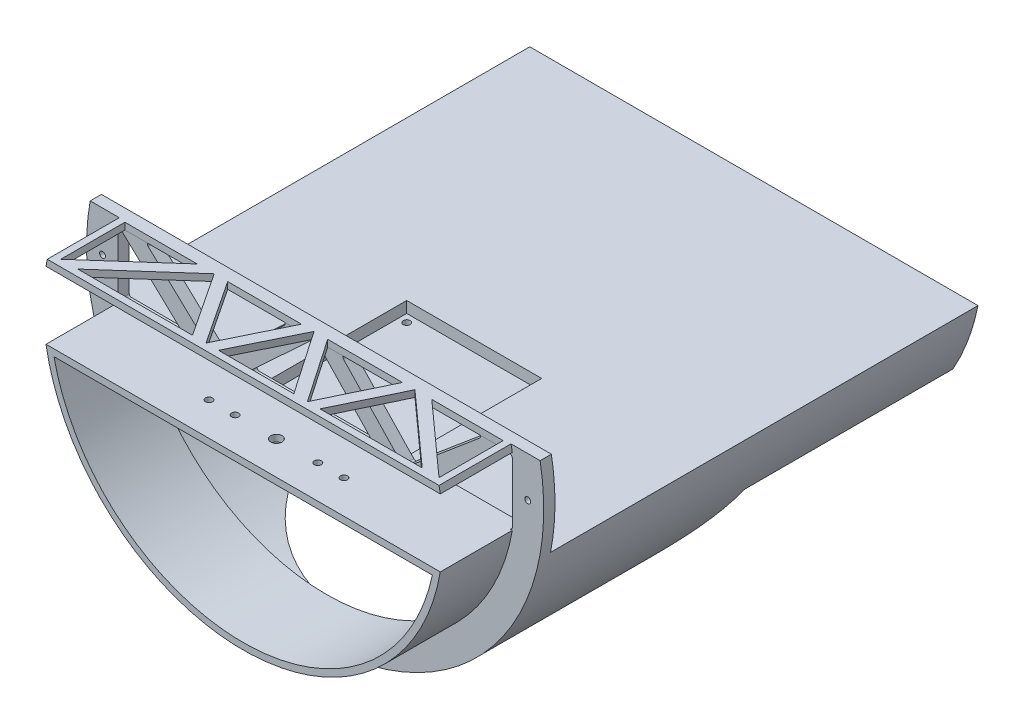
SolidWorks part; units mm, degrees
ref_plane "Front Plane" through (0, 0, 0) normal (0, 0, 1) x (1, 0, 0)
ref_plane "Top Plane" through (0, 0, 0) normal (0, 1, 0) x (1, 0, 0)
ref_plane "Right Plane" through (0, 0, 0) normal (1, 0, 0) x (0, 0, -1)
sketch "Sketch1" plane through (0, 0, 0) normal (0, 0, 1) x (1, 0, 0)
  circle A1 centre (0, 0) radius 101.6
  dimension "D3" = 203.2
extrude "Boss-Extrude1" add sketch "Sketch1" against normal blind 250
sketch "Sketch2" plane through (0, 0, 0) normal (0, 0, 1) x (1, 0, 0)
  line L0 (-87.6254, 15) -> (87.6254, 15)
  line L2 (87.6254, -15) -> (-87.6254, -15)
  circle A0 centre (0, 0) radius 88.9
  dimension "D1" = 177.8
  dimension "D2" = 30
extrude "Cut-Extrude1" cut sketch "Sketch2" against normal blind 32 contours L0 A0 L2 region at (0, 0, 0)
sketch "Sketch4" plane through (0, 0, 0) normal (0, 0, 1) x (1, 0, 0)
  circle A0 centre (0, 0) radius 101.6
  circle A1 centre (0, 0) radius 88.9
  dimension "D1" = 177.8
extrude "Cut-Extrude2" cut sketch "Sketch4" against normal blind 32
sketch "Sketch5" plane through (0, 0, -250) normal (0, 0, -1) x (-1, 0, 0)
  line L0 (-100.9298, -15) -> (-87.6254, -15)
  line L1 (87.6254, -15) -> (100.9298, -15)
  arc A0 (87.6254, -15) -> (-87.6254, -15) centre (0, 0) ccw
  arc A1 (100.9298, -15) -> (-100.9298, -15) centre (0, 0) ccw
  dimension "D1" = 177.8
  dimension "D2" = 15
extrude "Cut-Extrude3" cut sketch "Sketch5" against normal blind 213
sketch "Sketch7" plane through (0, 0, 0) normal (0, 1, 0) x (1, 0, 0)
  line L0 (-101.6, 37) -> (101.6, 37)
  line L1 (101.6, 37) -> (101.6, 291.2348)
  line L2 (101.6, 291.2348) -> (-101.6, 291.2348)
  line L3 (-101.6, 291.2348) -> (-101.6, 37)
extrude "Cut-Extrude5" cut sketch "Sketch7" against normal blind 20 and the other way blind 190
sketch "Sketch9" plane through (0, -20, 0) normal (0, 1, 0) x (1, 0, 0)
  line L0 (-99.612, 37) -> (99.612, 37) construction
  line L1 (-29.3117, 42) -> (30.6883, 42)
  line L2 (-29.3117, 42) -> (-29.3117, 102)
  line L3 (-29.3117, 102) -> (30.6883, 102)
  line L4 (30.6883, 42) -> (30.6883, 102)
  dimension "D1" = 60
  dimension "D2" = 60
  dimension "D3" = 5
extrude "Cut-Extrude6" cut sketch "Sketch9" against normal blind 5
sketch "Sketch11" plane through (0, 0, 0) normal (0, 0, 1) x (1, 0, 0)
  line L0 (-87.6254, 15) -> (87.6254, 15) construction
  line L1 (-128.703, 18) -> (126.4318, 18)
  line L2 (-128.703, 18) -> (-128.703, 107.221)
  line L3 (-128.703, 107.221) -> (126.4318, 107.221)
  line L4 (126.4318, 18) -> (126.4318, 107.221)
  dimension "D1" = 3
extrude "Cut-Extrude8" cut sketch "Sketch11" against normal blind 155
sketch "Sketch12" plane through (0, 0, 0) normal (0, 0, 1) x (1, 0, 0)
  line L0 (-84.0952, -18) -> (84.0952, -18)
  line L1 (87.6254, -15) -> (-87.6254, -15) construction
  arc A0 (-84.0952, -18) -> (84.0952, -18) centre (0, 0) ccw
  dimension "D1" = 172
  dimension "D2" = 3
extrude "Cut-Extrude9" cut sketch "Sketch12" against normal blind 34
sketch "Sketch14" plane through (0, 0, -250) normal (0, 0, -1) x (-1, 0, 0)
  line L0 (-82.8674, -23) -> (82.8674, -23)
  line L1 (99.612, -20) -> (-99.612, -20) construction
  arc A0 (-82.8674, -23) -> (82.8674, -23) centre (0, 0) ccw
  dimension "D1" = 3
  dimension "D2" = 86
extrude "Cut-Extrude10" cut sketch "Sketch14" against normal blind 143
sketch "Sketch15" plane through (0, 0, -107) normal (0, 0, -1) x (-1, 0, 0)
  line L3 (-89.6083, -39.9244) -> (-89.6083, -23)
  line L4 (-63.9724, -23) -> (-32.5, -23)
  line L5 (82.8674, -23) -> (-82.8674, -23) construction
  line L6 (89.6083, -39.9244) -> (89.6083, -23)
  line L7 (32.5, -35) -> (32.5, -23)
  line L8 (82.8674, -23) -> (-82.8674, -23) construction
  line L9 (32.5, -23) -> (63.9724, -23)
  line L10 (-32.5, -35) -> (-32.5, -23)
  line L14 (-32.5, -35) -> (32.5, -35)
  line L16 (-89.6083, -23) -> (-63.9724, -23)
  line L17 (63.9724, -23) -> (89.6083, -23)
  arc A0 (-89.6083, -39.9244) -> (89.6083, -39.9244) centre (0, 0) ccw
  arc A1 (-99.612, -20) -> (99.612, -20) centre (0, 0) ccw construction
  dimension "D1" = 3.5
  dimension "D3" = 65
extrude "Cut-Extrude12" cut sketch "Sketch15" against normal blind 70 and the other way blind 165
sketch "Sketch16" plane through (0, 0, -32) normal (0, 0, 1) x (1, 0, 0)
  line L0 (-87.6254, 15) -> (-55.8272, -15)
  line L1 (87.6254, -15) -> (-87.6254, -15) construction
  line L2 (87.6254, 15) -> (51.956, -15)
  line L3 (87.6254, -15) -> (-87.6254, -15) construction
  line L4 (-75.9677, 15) -> (-44.1695, -15)
  line L5 (-87.6254, 15) -> (87.6254, 15) construction
  line L6 (75.1966, 15) -> (39.5273, -15)
  line L7 (-87.6254, 15) -> (87.6254, 15) construction
  line L8 (-44.1695, -15) -> (-11.7741, 15)
  line L9 (-32.3954, -15) -> (0, 15)
  line L10 (39.5273, -15) -> (11.0334, 15)
  line L11 (28.4939, -15) -> (0, 15)
  line L12 (-87.6254, 15) -> (-87.6254, -15)
  line L13 (87.6254, 15) -> (87.6254, -15)
  line L14 (-87.6254, 15) -> (-75.9677, 15)
  line L15 (-55.8272, -15) -> (-32.3954, -15)
  line L16 (-32.3954, -15) -> (28.4939, -15)
  line L17 (28.4939, -15) -> (51.956, -15)
  line L18 (-87.6254, 15) -> (87.6254, 15)
  line L19 (-87.6254, -15) -> (87.6254, -15)
  line M13 (87.6254, 15) -> (-87.6254, 15)
  line M16 (-87.6254, -15) -> (87.6254, -15)
  dimension "D1" = 8
  dimension "D2" = 8
  dimension "D3" = 8
  dimension "D4" = 8
extrude "Cut-Extrude13" cut sketch "Sketch16" against normal blind 10 contours L0 L12 M16 | L4 L8 M13 | L11 L9 M16 | L10 L6 M13 | L13 L2 M16 region at (-77.026, -5, -32) region at (-43.9704, 5, -32) region at (-1.3005, -5, -32) region at (41.9191, 5, -32) region at (75.7356, -5, -32)
fillet "Fillet1" radius 1 15 edges at (-87.6254, 15, -34.5) (87.6254, 15, -34.5) (87.6254, -15, -34.5) (75.1966, 15, -34.5) (51.956, -15, -34.5) (-75.9677, 15, -34.5) (-87.6254, -15, -34.5) (-11.7741, 15, -34.5) (11.0334, 15, -34.5) (39.5273, -15, -34.5) (28.4939, -15, -34.5) (0, 15, -34.5) (-32.3954, -15, -34.5) (-44.1695, -15, -34.5) (-55.8272, -15, -34.5)
sketch "Sketch19" plane through (0, 18, 0) normal (0, 1, 0) x (1, 0, 0)
  line L1 (-44.3675, 31.5) -> (-25.5208, 3)
  line L2 (-38.3731, 31.5) -> (-19.5264, 3)
  line L4 (-19.5264, 3) -> (-5.5675, 31.5)
  line L7 (-87.0587, 0) -> (87.0587, 0) construction
  line L8 (-84.0587, 3) -> (84.0587, 3)
  line L9 (-84.0587, 3) -> (-84.0587, 31.5)
  line L10 (-84.0587, 31.5) -> (84.0587, 31.5)
  line L11 (84.0587, 3) -> (84.0587, 31.5)
  line L12 (-87.0587, 32) -> (-87.0587, 0) construction
  line L13 (87.0587, 0) -> (87.0587, 32) construction
  line L14 (99.9928, 37) -> (-99.9928, 37) construction
  line L15 (-84.0587, 3) -> (-51.9054, 31.5)
  line L16 (-44.3675, 31.5) -> (-76.5208, 3)
  line L17 (-13.9589, 3) -> (0, 31.5)
  line L18 (0, 31.5) -> (19.5177, 3)
  line L19 (6.0601, 31.5) -> (25.5778, 3)
  line L20 (25.5778, 3) -> (39.31, 31.5)
  line L21 (31.1279, 3) -> (44.8601, 31.5)
  line L22 (44.8601, 31.5) -> (76.5778, 3)
  line L23 (76.5778, 3) -> (84.0587, 3)
  line L24 (84.0587, 3) -> (52.341, 31.5)
  dimension "D1" = 3
  dimension "D2" = 3
  dimension "D3" = 3
  dimension "D4" = 5.5
  dimension "D5" = 5
  dimension "D6" = 5
  dimension "D7" = 5
  dimension "D8" = 5
  dimension "D9" = 5
  dimension "D10" = 5
  dimension "D11" = 38.8
  dimension "D12" = 38.8
  dimension "D13" = 51
  dimension "D14" = 51
extrude "Cut-Extrude14" cut sketch "Sketch19" against normal blind 10 contours L9 L15 L10 | L1 L16 L8 | L10 L2 L4 | L18 L17 L8 | L19 L20 L10 | L22 L21 L8 | L24 L11 L10 region at (-48.803, 18, -12.5) region at (-73.3409, 18, -22) region at (-21.1557, 18, -22) region at (1.8529, 18, -12.5) region at (23.6493, 18, -22) region at (50.8553, 18, -12.5) region at (73.4861, 18, -22)
sketch "Sketch21" plane through (0, -15, 0) normal (0, 1, 0) x (1, 0, 0)
  line L1 (87.6254, 32) -> (87.6254, 0) construction
  line L2 (-87.6254, 32) -> (-87.6254, 0) construction
  circle A0 centre (18.4, 14.8) radius 1.55
  circle A1 centre (-18.4, 14.8) radius 1.55
  circle A2 centre (0, 14.8) radius 2.5
  circle A3 centre (-30.0004, 14.8) radius 1.55
  circle A4 centre (30.0004, 14.8) radius 1.55
  dimension "D3" = 3.1
  dimension "D4" = 57.625
  dimension "D1" = 18.4
  dimension "D2" = 18.4
  dimension "D5" = 57.625
extrude "Cut-Extrude16" cut sketch "Sketch21" against normal blind 27
sketch "Sketch22" plane through (0, 0, -37) normal (0, 0, -1) x (-1, 0, 0)
  circle A1 centre (0, -94.5) radius 1.3
  circle A2 centre (94.5, 0) radius 1.3
  circle A3 centre (-94.5, 0) radius 1.3
  dimension "D2" = 2.6
extrude "Cut-Extrude17" cut sketch "Sketch22" against normal blind 10
sketch "Sketch23" plane through (0, -20, 0) normal (0, 1, 0) x (1, 0, 0)
  line L0 (30.6883, 102) -> (-29.3117, 102) construction
  line L1 (-118.6231, 227) -> (130.5087, 227)
  line L2 (-118.6231, 227) -> (-118.6231, 266.5535)
  line L3 (-118.6231, 266.5535) -> (130.5087, 266.5535)
  line L4 (130.5087, 227) -> (130.5087, 266.5535)
  dimension "D1" = 125
extrude "Cut-Extrude18" cut sketch "Sketch23" against normal blind 92
sketch "Sketch24" plane through (0, 0, -227) normal (0, 0, -1) x (-1, 0, 0)
  line L0 (-95.3657, -23) -> (95.3657, -23)
  line L2 (89.6083, -23) -> (-89.6083, -23) construction
  arc A0 (-95.3657, -23) -> (95.3657, -23) centre (0, 0) ccw
  arc A1 (-99.612, -20) -> (99.612, -20) centre (0, 0) ccw construction
  dimension "D1" = 3.5
  dimension "D2" = 0
sketch "Sketch25" plane through (0, 0, -37) normal (0, 0, -1) x (-1, 0, 0)
  line L0 (-82.8674, -23) -> (82.8674, -23)
  line L1 (-95.3657, -23) -> (95.3657, -23) construction
  arc A0 (-82.8674, -23) -> (82.8674, -23) centre (0, 0) ccw
  dimension "D1" = 172
  dimension "D2" = 0
extrude "Cut-Extrude20" cut sketch "Sketch25" against normal blind 120
sketch "Sketch26" plane through (0, 0, 0) normal (1, 0, 0) x (0, 0, -1)
  line L0 (227, -101.6) -> (227, -50)
  line L1 (227, -101.6) -> (42, -101.6)
  line L2 (227, -98.1) -> (227, -23) construction
  line L3 (227, -50) -> (134.5937, -50)
  line L4 (227, -20) -> (37, -20) construction
  line L5 (32, -101.6) -> (227, -101.6) construction
  line L6 (32, 18) -> (32, -101.6) construction
  spline S0 degree 3 poles (134.5937, -50) (115.8177, -84.2614) (67.2522, -74.712) (42, -101.6) knots 0 0 0 0 1 1 1 1
  dimension "D1" = 30
  dimension "D2" = 10
extrude "Cut-Extrude21" cut sketch "Sketch26" against normal blind 120 and the other way blind 120
extrude "Cut-Extrude22" cut sketch "Sketch24" against normal blind 120
sketch "Sketch27" plane through (0, -25, 0) normal (0, 1, 0) x (1, 0, 0)
  line L0 (-29.3117, 102) -> (-29.3117, 42) construction
  line L2 (-29.3117, 42) -> (30.6883, 42) construction
  circle A0 centre (-25.8117, 98.5) radius 1.55
  circle A1 centre (27.1883, 98.5) radius 1.55
  circle A2 centre (27.1883, 45.5) radius 1.55
  circle A3 centre (-25.8117, 45.5) radius 1.55
  dimension "D1" = 3.1
  dimension "D2" = 53
  dimension "D3" = 53
  dimension "D4" = 53
  dimension "D5" = 3.5
  dimension "D6" = 3.5
extrude "Cut-Extrude23" cut sketch "Sketch27" against normal blind 16
